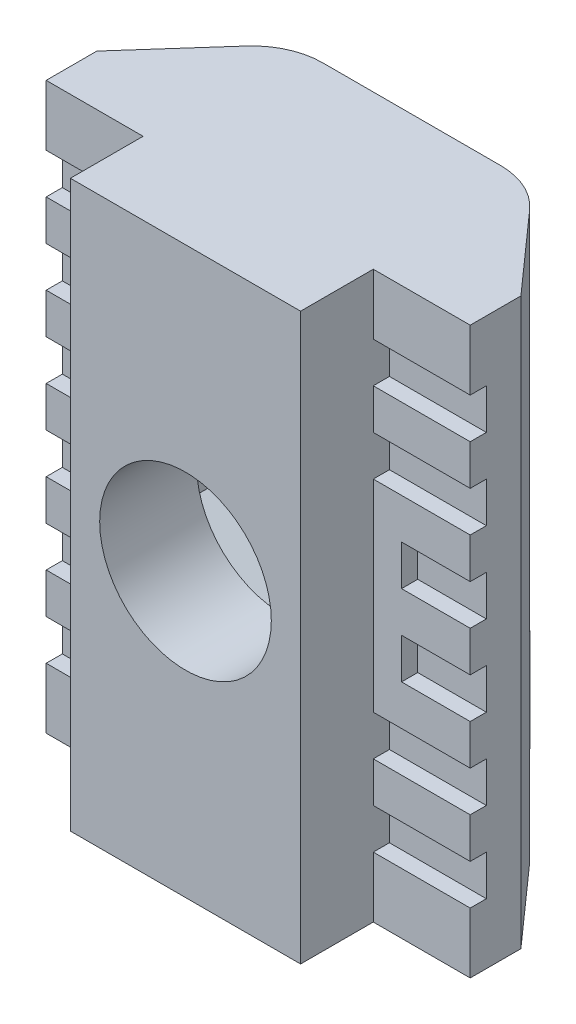
SolidWorks part; units mm, degrees
ref_plane "Front Plane" through (0, 0, 0) normal (0, 0, 1) x (1, 0, 0)
ref_plane "Top Plane" through (0, 0, 0) normal (0, 1, 0) x (1, 0, 0)
ref_plane "Right Plane" through (0, 0, 0) normal (1, 0, 0) x (0, 0, -1)
sketch "Sketch1" plane through (0, 0, 0) normal (0, 1, 0) x (1, 0, 0)
  line L0 (3.6967, 2.3787) -> (5.5, 0.35)
  line L1 (-3.1, -3.05) -> (3.1, -3.05)
  line L2 (-5.5, -1.25) -> (-5.5, 0.35)
  line L3 (-2.2019, 3.05) -> (2.2019, 3.05)
  line L4 (5.5, -1.25) -> (5.5, 0.35)
  line L5 (-3.6967, 2.3787) -> (-5.5, 0.35)
  line L6 (-5.5, -1.25) -> (-3.1, -1.25)
  line L7 (-3.1, -1.25) -> (-3.1, -3.05)
  line L8 (5.5, -1.25) -> (3.1, -1.25)
  line L9 (3.1, -1.25) -> (3.1, -3.05)
  line L10 (-3.5098, 2.2126) -> (-5.25, 0.255)
  line L11 (-5.25, -1) -> (-5.25, 0.255)
  line L12 (-5.25, -1) -> (-2.85, -1)
  line L13 (-2.85, -1) -> (-2.85, -2.8)
  line L14 (-2.85, -2.8) -> (2.85, -2.8)
  line L15 (2.85, -1) -> (2.85, -2.8)
  line L16 (5.25, -1) -> (2.85, -1)
  line L17 (5.25, -1) -> (5.25, 0.255)
  line L18 (3.5098, 2.2126) -> (5.25, 0.255)
  line L19 (-2.2019, 2.8) -> (2.2019, 2.8)
  arc A0 (2.2019, 3.05) -> (3.6967, 2.3787) centre (2.2019, 1.05) cw
  arc A1 (-2.2019, 3.05) -> (-3.6967, 2.3787) centre (-2.2019, 1.05) ccw
  arc A2 (2.2019, 2.8) -> (3.5098, 2.2126) centre (2.2019, 1.05) cw
  arc A3 (-2.2019, 2.8) -> (-3.5098, 2.2126) centre (-2.2019, 1.05) ccw
  point P2 (3.1, 3.05)
  point P16 (-3.1, 3.05)
  dimension "D5" = 2
  dimension "D1" = 5.5
  dimension "D2" = 5.5
  dimension "D3" = 3.05
  dimension "D4" = 3.05
  dimension "D6" = 0.25
  dimension "D7" = 6.2
  dimension "D10" = 6.2
extrude "Boss-Extrude1" add sketch "Sketch1" along normal blind 14 contours L10 L11 L12 L13 L14 L15 L16 L17 L18 A2 L19 A3
sketch "Sketch2" plane through (0, 0, -2.8) normal (0, 0, -1) x (-1, 0, 0)
  line L0 (2.85, 0) -> (-2.85, 0) construction
  line L1 (-3.55, 4.9504) -> (0, 2.9008)
  line L2 (0, 2.9008) -> (3.55, 4.9504)
  line L3 (3.55, 4.9504) -> (3.55, 9.0496)
  line L4 (3.55, 9.0496) -> (0, 11.0992)
  line L5 (0, 11.0992) -> (-3.55, 9.0496)
  line L6 (-3.55, 9.0496) -> (-3.55, 4.9504)
  circle A0 centre (0, 7) radius 3.55 construction
  dimension "D1" = 7
extrude "Cut-Extrude1" cut sketch "Sketch2" against normal blind 3.2
sketch "Sketch4" plane through (-2.85, 0, 0) normal (-1, 0, 0) x (0, 0, 1)
  line L0 (1, 14) -> (1, 0) construction
  line L1 (1, 12.5) -> (0.6, 12.5)
  line L2 (1, 12.5) -> (1, 11.5)
  line L3 (1, 11.5) -> (0.6, 11.5)
  line L4 (0.6, 12.5) -> (0.6, 11.5)
  line L6 (1, 10.5) -> (0.6, 10.5)
  line L7 (1, 10.5) -> (1, 9.5)
  line L8 (1, 9.5) -> (0.6, 9.5)
  line L9 (0.6, 10.5) -> (0.6, 9.5)
  line L10 (1, 8.5) -> (0.6, 8.5)
  line L11 (1, 8.5) -> (1, 7.5)
  line L12 (1, 7.5) -> (0.6, 7.5)
  line L13 (0.6, 8.5) -> (0.6, 7.5)
  line L14 (1, 6.5) -> (0.6, 6.5)
  line L15 (1, 6.5) -> (1, 5.5)
  line L16 (1, 5.5) -> (0.6, 5.5)
  line L17 (0.6, 6.5) -> (0.6, 5.5)
  line L18 (1, 4.5) -> (0.6, 4.5)
  line L19 (1, 4.5) -> (1, 3.5)
  line L20 (1, 3.5) -> (0.6, 3.5)
  line L21 (0.6, 4.5) -> (0.6, 3.5)
  line L22 (1, 2.5) -> (0.6, 2.5)
  line L23 (1, 2.5) -> (1, 1.5)
  line L24 (1, 1.5) -> (0.6, 1.5)
  line L25 (0.6, 2.5) -> (0.6, 1.5)
  dimension "D1" = 1.5
  dimension "D2" = 1
  dimension "D3" = 1
  dimension "D4" = 1
  dimension "D5" = 1
  dimension "D6" = 1
  dimension "D7" = 1
  dimension "D8" = 1
  dimension "D9" = 1
  dimension "D10" = 1
  dimension "D11" = 1
  dimension "D12" = 0.4
  dimension "D13" = 0.4
  dimension "D14" = 1
  dimension "D15" = 0.4
  dimension "D16" = 0.4
  dimension "D17" = 0.4
  dimension "D18" = 0.4
extrude "Cut-Extrude3" cut sketch "Sketch4" along normal through all
mirror "Mirror1" about plane through (0, 0, 0) normal (1, 0, 0) of "Cut-Extrude3"
extrude "Boss-Extrude2" add sketch "Sketch2<2>" against normal up to surface (3.8 mm away) from surface up to face at (-4.05, 7, 1) starting at face at (0, 7, 0.4)
sketch "Sketch2<2>" plane through (0, 0, -2.8) normal (0, 0, -1) x (-1, 0, 0) same geometry as "Sketch2"
sketch "Sketch3" plane through (0, 0, 2.8) normal (0, 0, 1) x (1, 0, 0)
  line L0 (-2.85, 0) -> (2.85, 0) construction
  circle A0 centre (0, 7) radius 2.125
  dimension "D1" = 7
  dimension "D2" = 4.25
extrude "Cut-Extrude2" cut sketch "Sketch3" against normal through all
